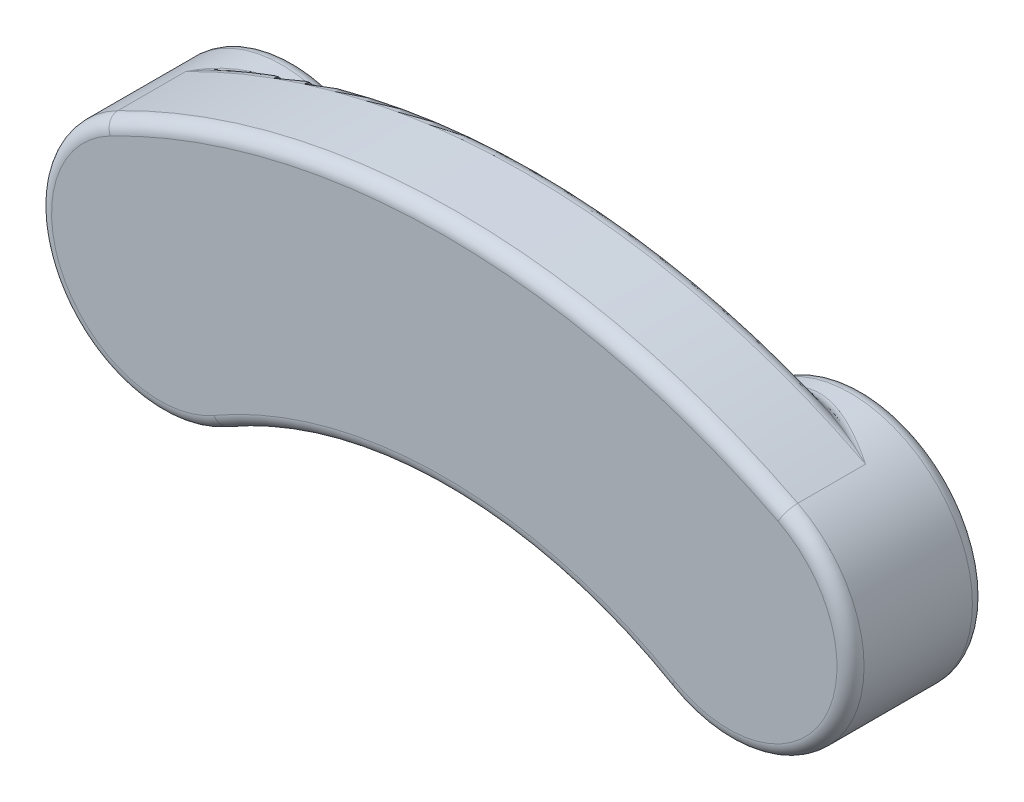
SolidWorks part; units mm, degrees
ref_plane "Front Plane" through (0, 0, 0) normal (0, 0, 1) x (1, 0, 0)
ref_plane "Top Plane" through (0, 0, 0) normal (0, 1, 0) x (1, 0, 0)
ref_plane "Right Plane" through (0, 0, 0) normal (1, 0, 0) x (0, 0, -1)
sketch "Sketch1" plane through (0, 0, 0) normal (0, 0, 1) x (1, 0, 0)
  line L0 (30, 0) -> (-30, 0)
  circle A0 centre (-21, 0) radius 9
  circle A2 centre (21, 0) radius 9
  point P6 (0, 0)
  point P9 (0, 0)
  dimension "D1" = 18
  dimension "D2" = 60
extrude "Boss-Extrude1" add sketch "Sketch1" against normal blind 10 contours L0 A0 | L0 A0 | L0 A2 | L0 A2 region at (-21, -3.8197, 0) region at (21, 3.8197, 0) region at (21, -3.8197, 0) region at (-21, 3.8197, 0)
sketch "Sketch2" plane through (0, 0, 0) normal (0, 0, 1) x (1, 0, 0)
  arc A0 (-25.1087, 8.0074) -> (25.1087, 8.0074) centre (0, -40.9268) cw
  circle A1 centre (-21, 0) radius 9 construction
  circle A2 centre (21, 0) radius 9 construction
  arc A3 (-16.5, -7.7942) -> (16.5, -7.7942) centre (0, -36.3731) cw
  arc A4 (-25.1087, 8.0074) -> (-16.5, -7.7942) centre (-21, 0) cw
  arc A5 (16.5, -7.7942) -> (25.1087, 8.0074) centre (21, 0) cw
  dimension "D1" = 55
  dimension "D2" = 33
extrude "Boss-Extrude2" add sketch "Sketch2" against normal blind 7 contours A5 A0 A4 A3
sketch "Sketch3" plane through (0, 0, -10) normal (0, 0, -1) x (-1, 0, 0)
  line L0 (-17.7707, 0.545) -> (-24.2293, 0.545)
  line L1 (-17.7707, -0.545) -> (-24.2293, -0.545)
  line L2 (-21, 9) -> (-21, -9) construction
  line L3 (24.2293, 0.545) -> (17.7707, 0.545)
  line L4 (24.2293, -0.545) -> (17.7707, -0.545)
  line L5 (21, -9) -> (21, 9) construction
  arc A0 (-24.2293, -0.545) -> (-17.7707, -0.545) centre (-21, 0) ccw
  arc A1 (-17.7707, 0.545) -> (-24.2293, 0.545) centre (-21, 0) ccw
  arc A2 (-16.5, -7.7942) -> (-25.1087, 8.0074) centre (-21, 0) ccw construction
  circle A3 centre (-21, 0) radius 9 construction
  arc A4 (17.7707, -0.545) -> (24.2293, -0.545) centre (21, 0) ccw
  arc A5 (24.2293, 0.545) -> (17.7707, 0.545) centre (21, 0) ccw
  circle A6 centre (21, 0) radius 9 construction
  arc A7 (25.1087, 8.0074) -> (16.5, -7.7942) centre (21, 0) ccw construction
  point P3 (-21, 0.545)
  point P6 (-21, -0.545)
  point P15 (-21, 0)
  point P19 (21, 0.545)
  point P22 (21, -0.545)
  point P31 (21, 0)
  dimension "D1" = 6.55
  dimension "D5" = 6.55
  dimension "D2" = 0.545
  dimension "D3" = 1.09
  dimension "D4" = 0
  dimension "D6" = 1.09
  dimension "D7" = 0.545
  dimension "D8" = 0
extrude "Cut-Extrude1" cut sketch "Sketch3" against normal blind 7
fillet "Fillet1" radius 1 10 edges at (0, -3.3731, 0) (28.9032, -4.3057, 0) (-12, 0, -10) (-28.9032, -4.3057, 0) (-13.0968, 4.3057, -7) (30, 0, -10) (13.0968, 4.3057, -7) (0, -3.3731, -7) (0, 14.0732, -7) (0, 14.0732, 0)
